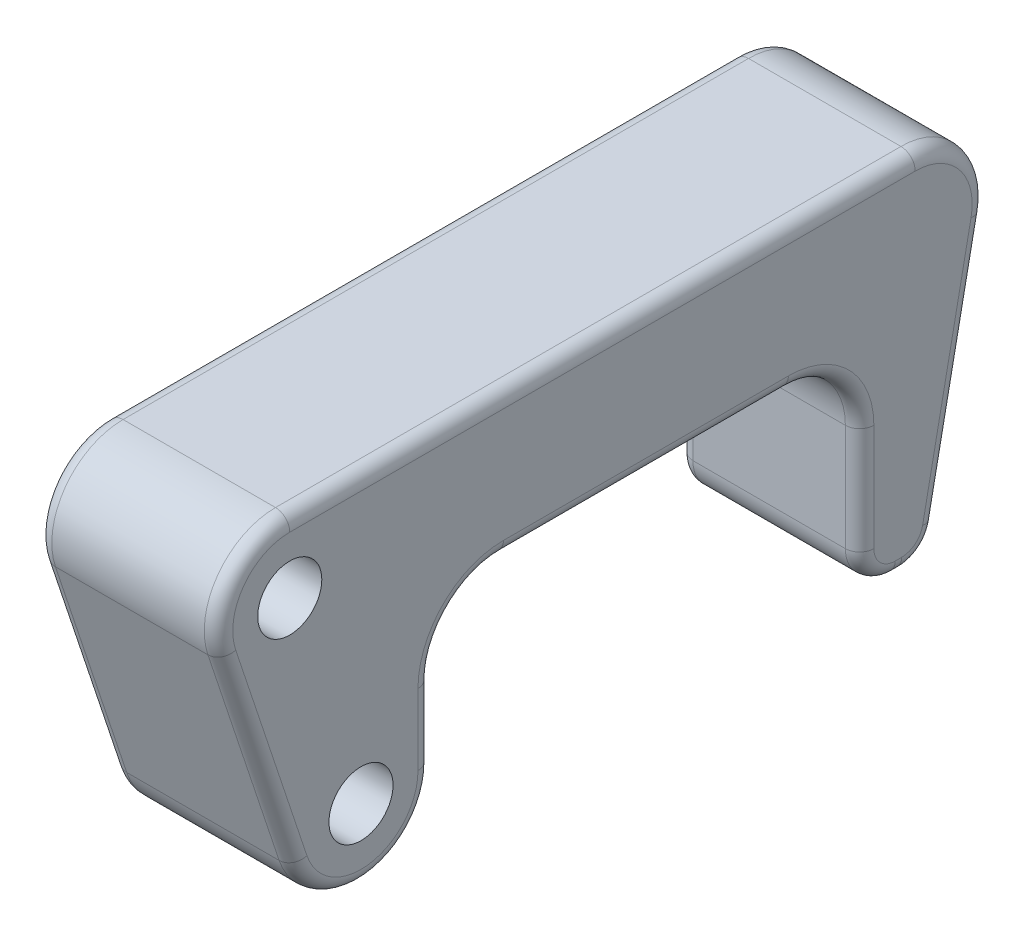
SolidWorks part; units mm, degrees
ref_plane "Front Plane" through (0, 0, 0) normal (0, 0, 1) x (1, 0, 0)
ref_plane "Top Plane" through (0, 0, 0) normal (0, 1, 0) x (1, 0, 0)
ref_plane "Right Plane" through (0, 0, 0) normal (1, 0, 0) x (0, 0, -1)
sketch "Sketch1" plane through (0, 0, 0) normal (1, 0, 0) x (0, 0, -1)
  line L6 (-4.7434, -1.5811) -> (0.2566, -16.5811)
  line L7 (0, 5) -> (50, 5)
  line L8 (40, -20) -> (45, -20)
  line L9 (40, -20) -> (40, -5)
  line L10 (40, -5) -> (10, -5)
  line L11 (10, -5) -> (10, -15)
  line L12 (45, -20) -> (50, 5)
  circle A3 centre (0, 0) radius 2.25
  circle A4 centre (5, -15) radius 2.25
  circle A5 centre (0, 0) radius 5
  circle A6 centre (5, -15) radius 5
  dimension "D2" = 4.5
  dimension "D1" = 4.5
  dimension "D3" = 10
  dimension "D4" = 10
  dimension "D5" = 10
  dimension "D6" = 15
  dimension "D7" = 30
  dimension "D8" = 10
  dimension "D9" = 15
  dimension "D10" = 5
  dimension "D11" = 5
extrude "Boss-Extrude1" add sketch "Sketch1" along normal blind 12.7 contours A4 A3 | L10 | A6 A4 region at (0, -2.8826, -26.025) region at (0, 2.8409, 3.9415) region at (0, -10.2042, -4.2217)
fillet "Fillet1" radius 5 3 edges at (6.35, -5, -40) (6.35, 5, -50) (6.35, -5, -10)
fillet "Fillet2" radius 2.5 2 edges at (6.35, -20, -45) (6.35, -20, -40)
fillet "Fillet3" radius 1 28 edges at (0, -6.4645, -38.5355) (0, -13.75, -40) (0, -19.2678, -40.7322) (0, -20, -42.7252) (0, -19.4334, -44.5355) (0, -9.4854, -47.1029) (0, 3.1699, -47.7677) (0, 5, -21.9505) (0, 2.9236, 4.0562) (0, -9.0811, 2.2434) (0, -19.9354, -5.8009) (0, -12.5, -10) (0, -6.4645, -11.4645) (12.7, -6.4645, -38.5355) (12.7, -13.75, -40) (12.7, -19.2678, -40.7322) (12.7, -20, -42.7252) (12.7, -19.4334, -44.5355) (12.7, -9.4854, -47.1029) (12.7, 3.1699, -47.7677) (12.7, 5, -21.9505) (12.7, 2.9236, 4.0562) (12.7, -9.0811, 2.2434) (12.7, -19.9354, -5.8009) (12.7, -12.5, -10) (12.7, -6.4645, -11.4645) (0, -5, -25) (12.7, -5, -25)
